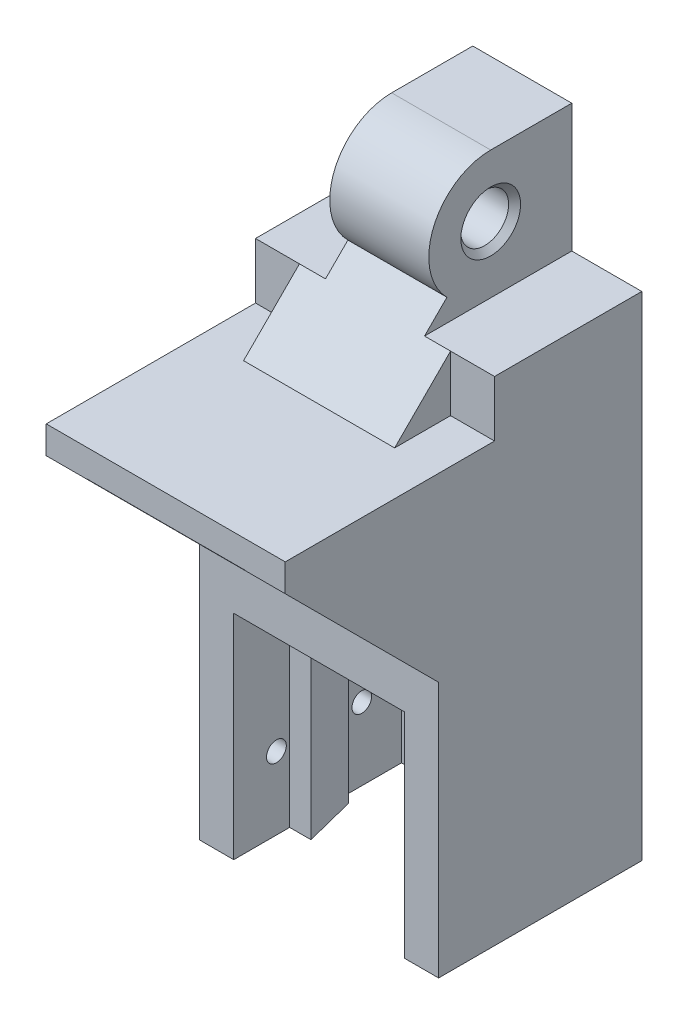
SolidWorks part; units mm, degrees
material "Plastique personnalisé"
ref_plane "前视基准面" through (0, 0, 0) normal (0, 0, 1) x (1, 0, 0)
ref_plane "上视基准面" through (0, 0, 0) normal (0, 1, 0) x (1, 0, 0)
ref_plane "右视基准面" through (0, 0, 0) normal (1, 0, 0) x (0, 0, -1)
sketch "Sketch1" plane through (0, 0, 0) normal (0, 1, 0) x (1, 0, 0)
  line L1 (-13, 14) -> (13, 14)
  line L2 (-13, 14) -> (-13, -14)
  line L3 (-13, -14) -> (13, -14)
  line L4 (13, 14) -> (13, -14)
  line L5 (-13, 14) -> (13, -14) construction
  line L6 (-13, -14) -> (13, 14) construction
  point P0 (0, 0)
  dimension "D1" = 26
  dimension "D2" = 28
extrude "Boss-Extrude1" add sketch "Sketch1" along normal blind 50
sketch "Sketch7" plane through (13, 0, 0) normal (1, 0, 0) x (0, 0, -1)
  line L0 (4.5, 50) -> (-14, 50)
  line L1 (-14, 50) -> (-14, 24)
  line L2 (-14, 50) -> (-14, 0) construction
  line L3 (-14, 24) -> (-0.6265, 37.3735)
  line L4 (7.5, 35.3637) -> (14, 50) construction
  line L6 (14, 50) -> (14, 0) construction
  line L7 (14, 42.5) -> (4.5, 42.5) construction
  line L8 (4.5, 49.75) -> (14, 49.75)
  line L9 (14, 49.75) -> (14, 50)
  line L10 (14, 50) -> (4.5, 50)
  arc A1 (-0.6265, 37.3735) -> (4.5, 49.75) centre (4.5, 42.5) ccw
  dimension "D2" = 7.5
  dimension "D1" = 26
  dimension "D3" = 9.5
  dimension "D4" = 45
extrude "Cut-Extrude3" cut sketch "Sketch7" against normal blind 39
sketch "Sketch14" plane through (0, 0, 0) normal (1, 0, 0) x (0, 0, -1)
  line L0 (14, 49.75) -> (14, 0) construction
  circle A0 centre (4.5, 42.5) radius 7.25
  dimension "D2" = 14.5
  dimension "D1" = 9.5
extrude "Boss-Extrude7" add sketch "Sketch14" against normal blind 5.8 and the other way blind 5.8
mirror "Symétrie1" about plane through (0, 0, 0) normal (1, 0, 0) of "Boss-Extrude7"
sketch "Sketch15" plane through (13, 0, 0) normal (1, 0, 0) x (0, 0, -1)
  line L0 (14, 49.75) -> (14, 0) construction
  line L1 (4.5, 42.5) -> (1.6109, 40.6109) construction
  line L3 (4.5, 49.75) -> (14, 49.75) construction
  circle A1 centre (4.5, 42.5) radius 2.8
  dimension "D1" = 5.6
  dimension "D2" = 9.5
  dimension "D3" = 7.25
extrude "Cut-Extrude4" cut sketch "Sketch15" against normal blind 28
sketch "Sketch16" plane through (13, 0, 0) normal (1, 0, 0) x (0, 0, -1)
  circle A0 centre (4.5, 42.5) radius 5.25
  dimension "D1" = 10.5
sketch "Sketch17" plane through (0, 0, 0) normal (0, -1, 0) x (1, 0, 0)
  line L0 (-9.3, 3.25) -> (-13, 3.25)
  line L2 (9.3, 3.25) -> (9.3, 9.8)
  line L3 (-13, -14) -> (-13, 14) construction
  line L4 (-13, 3.25) -> (-13, 14)
  line L5 (-9.3, 3.25) -> (-9.3, 9.8)
  line L6 (-13, 14) -> (13, 14)
  line L8 (13, 14) -> (13, 3.25)
  line L9 (13, 14) -> (13, -14) construction
  line L10 (13, 3.25) -> (9.3, 3.25)
  line L14 (9.3, 9.8) -> (-9.3, 9.8)
extrude "Cut-Extrude7" cut sketch "Sketch17" against normal through all
sketch "Sketch18" plane through (0, 0, 0) normal (1, 0, 0) x (0, 0, -1)
  line L3 (-2.2308, 35.7692) -> (-5.9308, 32.0692)
  line L6 (-2.2308, 35.7692) -> (-5.9308, 35.7692)
  line L7 (-5.9308, 35.7692) -> (-5.9308, 32.0692)
  dimension "D1" = 3.7
  dimension "D3" = 3.7
sketch "Sketch19" plane through (0, 0, -14) normal (0, 0, -1) x (-1, 0, 0)
  line L0 (-13, 0) -> (13, 0) construction
  circle A0 centre (0, 16) radius 2.15
  point P2 (0, 0)
  dimension "D1" = 4.3
  dimension "D2" = 16
extrude "Cut-Extrude9" cut sketch "Sketch19" against normal blind 50
sketch "Sketch20" plane through (0, 0, -14) normal (0, 0, -1) x (-1, 0, 0)
  circle A0 centre (0, 16) radius 4
  dimension "D1" = 8
extrude "Cut-Extrude10" [suppressed] cut sketch "Sketch20" against normal blind 3
sketch "Esquisse1" plane through (0, 49.75, 0) normal (0, 1, 0) x (1, 0, 0)
  line L2 (-5.8, 4.5) -> (-23.1712, 4.5)
  line L3 (-5.8, 4.5) -> (-5.8, 15.3551)
  line L4 (-5.8, 15.3551) -> (-23.1712, 15.3551)
  line L5 (-23.1712, 4.5) -> (-23.1712, 15.3551)
extrude "Enlèv. mat.-Extru.1" cut sketch "Esquisse1" against normal blind 7.5
mirror "Symétrie3" about plane through (0, 0, 0) normal (1, 0, 0) of "Enlèv. mat.-Extru.1"
extrude "Boss.-Extru.1" [suppressed] add sketch "Sketch18" along normal blind 3.4 and the other way blind 3.4
sketch "Esquisse3" plane through (13, 0, 0) normal (1, 0, 0) x (0, 0, -1)
  line L0 (-3.25, 34.75) -> (14, 34.75)
  line L1 (14, 42.25) -> (14, 0) construction
  line L2 (14, 34.75) -> (14, 43.174)
  line L3 (14, 42.25) -> (14, 49.75) construction
  line L4 (14, 43.174) -> (-3.25, 43.174)
  line L5 (-3.25, 43.174) -> (-3.25, 34.75)
extrude "Enlèv. mat.-Extru.3" cut sketch "Esquisse3" against normal up to vertex (7.2 mm away) up to point (5.8, 37.3735, 0.6265)
mirror "Symétrie4" about plane through (0, 0, 0) normal (1, 0, 0) of "Enlèv. mat.-Extru.3"
sketch "Esquisse43" plane through (0, 0, 9.8) normal (0, 0, 1) x (1, 0, 0)
  line L1 (-9.3, 28.2) -> (-9.3, 0) construction
  line L2 (9.3, 28.2) -> (9.3, 0) construction
  line L3 (-9.3, 25) -> (9.3, 25)
  line L4 (-9.3, 25) -> (-9.3, 7)
  line L5 (-9.3, 7) -> (9.3, 7)
  line L6 (9.3, 25) -> (9.3, 7)
  dimension "D2" = 18
extrude "Enlèv. mat.-Extru.4" cut sketch "Esquisse43" against normal blind 20
sketch "Esquisse45" plane through (0, 0, 0) normal (0, -1, 0) x (1, 0, 0)
  line L0 (-9.3, 3.25) -> (-9.3, 9.8)
  line L1 (-9.3, 9.8) -> (9.3, 9.8)
  line L2 (9.3, 9.8) -> (9.3, 3.25)
  line L3 (9.3, 3.25) -> (13, 3.25)
  line L4 (13, 3.25) -> (13, -14)
  line L5 (13, -14) -> (-13, -14)
  line L6 (-13, -14) -> (-13, 3.25)
  line L7 (-13, 3.25) -> (-9.3, 3.25)
extrude "Boss.-Extru.28" add sketch "Esquisse45" along normal blind 23
sketch "Sketch3" plane through (0, -23, 0) normal (0, 1, 0) x (1, 0, 0)
  line L0 (10, 2.65) -> (10, 9.85)
  line L1 (2.9, 9.85) -> (10, 9.85)
  line L2 (-10, 9.85) -> (-10, 2.65)
  line L3 (-10, 9.85) -> (-2.9, 9.85)
  line L4 (-10, -14.9617) -> (-10, -3.25)
  line L5 (7.5, -3.25) -> (9, 2.65)
  line L6 (-10, -14.9617) -> (10, -14.9617)
  line L7 (2.9, 9.85) -> (2.9, 5.85) construction
  line L8 (-10, -3.25) -> (-7.5028, -3.25) construction
  line L10 (2.9, 5.85) -> (-2.9, 5.85) construction
  line L11 (10, -14.9617) -> (10, -3.25)
  line L12 (10, -3.25) -> (7.5, -3.25)
  line L13 (-10, 2.65) -> (-9, 2.65)
  line L14 (10, 2.65) -> (9, 2.65)
  line L15 (-10, -3.25) -> (-7.5028, -3.25)
  line L16 (-2.9, 9.85) -> (-2.9, 5.85) construction
  line L17 (-7.5028, -3.25) -> (-9, 2.65)
  line L31 (2.9, 9.85) -> (2.9, 5.85)
  line L32 (2.9, 5.85) -> (-2.9, 5.85)
  line L33 (-2.9, 5.85) -> (-2.9, 9.85)
  dimension "D3" = 5.8
  dimension "D4" = 1
  dimension "D5" = 5.9
  dimension "D6" = 7.2
  dimension "D7" = 1
  dimension "D1" = 7.1
  dimension "D2" = 7.1
  dimension "D9" = 7.2
extrude "Enlèv. mat.-Extru.5" cut sketch "Sketch3" along normal blind 25
sketch "Esquisse47" plane through (0, 2, 0) normal (0, -1, 0) x (-1, 0, 0)
  line L0 (0, 0) -> (0, -7.2291) construction
  line L1 (-9, 2.65) -> (-9, 5.85)
  line L2 (-9, 2.65) -> (-7.0167, -5.49)
  line L3 (6.5509, 5.85) -> (9, 5.85)
  line L4 (6.5509, -5.49) -> (7.0167, -5.49)
  line L5 (-6.5509, -5.49) -> (-7.0167, -5.49)
  line L7 (9, 2.65) -> (7.0167, -5.49)
  line L8 (-6.5509, 5.85) -> (-9, 5.85)
  line L9 (9, 2.65) -> (9, 5.85)
  line L10 (2.9, 0.55) -> (2.9, 6.65) construction
  arc A0 (6.5509, -5.49) -> (6.5509, 5.85) centre (9.1283, 0.18) cw
  arc A1 (-6.5509, -5.49) -> (-6.5509, 5.85) centre (-9.1283, 0.18) ccw
extrude "Enlèv. mat.-Extru.6" cut sketch "Esquisse47" against normal blind 7
sketch "Esquisse48" plane through (0, 0, -10.2) normal (0, 0, 1) x (1, 0, 0)
  circle A0 centre (0, 16) radius 4
  dimension "D1" = 8
extrude "Boss.-Extru.29" add sketch "Esquisse48" along normal blind 6
sketch "Esquisse49" [suppressed] plane through (0, 0, -10.2) normal (0, 0, -1) x (-1, 0, 0)
  line L0 (0, 18.15) -> (0, 13.85) construction
  circle A0 centre (0, 16) radius 2.15 construction
  circle A1 centre (0, 16) radius 2.15 construction
  circle A2 centre (0, 16) radius 2.15
extrude "Enlèv. mat.-Extru.7" [suppressed] cut sketch "Esquisse49" against normal blind 5
sketch "Esquisse50" [suppressed] plane through (0, 0, -5.2) normal (0, 0, -1) x (-1, 0, 0)
  circle A0 centre (0, 16) radius 2.15
extrude "Enlèv. mat.-Extru.8" [suppressed] cut sketch "Esquisse50" against normal blind 5
sketch "Esquisse51" plane through (0, 0, -5.85) normal (0, 0, 1) x (1, 0, 0)
  line L0 (2.9, 2) -> (-2.9, 2) construction
  circle A0 centre (0, -8) radius 2.15
  dimension "D1" = 4.3
  dimension "D2" = 10
extrude "Enlèv. mat.-Extru.9" cut sketch "Esquisse51" against normal blind 12 contours A0
sketch "Esquisse52" plane through (0, 0, -14) normal (0, 0, -1) x (-1, 0, 0)
  circle A0 centre (0, -8) radius 3.5
  dimension "D1" = 7
extrude "Enlèv. mat.-Extru.10" [suppressed] cut sketch "Esquisse52" against normal blind 3 contours A0
sketch "Esquisse53" plane through (-9.3, 0, 0) normal (-1, 0, 0) x (0, 0, 1)
  line L1 (9.8, 28.2) -> (3.25, 28.2)
  line L2 (9.8, 28.2) -> (9.8, 2)
  line L3 (9.8, 2) -> (3.25, 2)
  line L4 (3.25, 28.2) -> (3.25, 2)
extrude "Boss.-Extru.30" add sketch "Esquisse53" along normal up to vertex (3.7 mm away) up to point (-13, 34.75, 3.25)
sketch "Esquisse54" plane through (9.3, 0, 0) normal (1, 0, 0) x (0, 0, -1)
  line L1 (-9.8, 28.2) -> (-3.25, 28.2)
  line L2 (-9.8, 28.2) -> (-9.8, 2)
  line L3 (-9.8, 2) -> (-3.25, 2)
  line L4 (-3.25, 28.2) -> (-3.25, 2)
extrude "Boss.-Extru.31" add sketch "Esquisse54" along normal up to vertex (3.7 mm away) up to point (13, -23, 3.25)
sketch "Esquisse55" plane through (0, 0, 3.25) normal (0, 0, 1) x (1, 0, 0)
  line L0 (-7.5028, -23) -> (-13, -23) construction
  line L1 (-13, 2) -> (-10, 2)
  line L2 (-13, 2) -> (-13, -23)
  line L3 (-13, -23) -> (-10, -23)
  line L4 (-10, 2) -> (-10, -23)
  line L5 (13, -23) -> (7.5, -23) construction
  line L6 (13, 2) -> (10, 2)
  line L7 (13, 2) -> (13, -23)
  line L8 (13, -23) -> (10, -23)
  line L9 (10, 2) -> (10, -23)
  dimension "D1" = 3
  dimension "D2" = 3
extrude "Boss.-Extru.32" add sketch "Esquisse55" along normal up to vertex (6.55 mm away) up to point (-13, 2, 9.8)
sketch "Esquisse56" plane through (-13, 0, 0) normal (-1, 0, 0) x (0, 0, 1)
  line L0 (9.8, -23) -> (9.8, 28.2) construction
  line L2 (9.8, -23) -> (-14, -23) construction
  circle A0 centre (-5.2, -14.5) radius 1.15
  circle A1 centre (4.8, -14.5) radius 1.16
  dimension "D1" = 2.3
  dimension "D2" = 2.32
  dimension "D3" = 10
  dimension "D4" = 5
  dimension "D5" = 8.5
extrude "Enlèv. mat.-Extru.11" cut sketch "Esquisse56" against normal blind 10
chamfer "Chanfrein1" distance 0.7 angle 45 2 edges at (5.8, 42.5, -7.3) (-5.8, 42.5, -7.3)
sketch "Esquisse57" plane through (0, 0, -10.2) normal (0, 0, -1) x (-1, 0, 0)
  circle A0 centre (0, 16) radius 2.15
extrude "Enlèv. mat.-Extru.12" cut sketch "Esquisse57" against normal blind 10
sketch "Esquisse58" plane through (-13, 0, 0) normal (-1, 0, 0) x (0, 0, 1)
  line L0 (-14, 34.75) -> (3.25, 34.75)
  line L1 (3.25, 34.75) -> (3.25, 28.2)
  line L2 (3.25, 28.2) -> (9.8, 28.2)
  line L3 (9.8, 28.2) -> (9.8, -23)
  line L4 (9.8, -23) -> (-14, -23)
  line L5 (-14, -23) -> (-14, 34.75)
  circle A0 centre (-5.2, -14.5) radius 1.15
  circle A1 centre (4.8, -14.5) radius 1.16
extrude "Boss.-Extru.33" add sketch "Esquisse58" along normal blind 1
sketch "Esquisse59" plane through (13, 0, 0) normal (1, 0, 0) x (0, 0, -1)
  line L0 (-3.25, 28.2) -> (-3.25, 34.75)
  line L1 (-3.25, 34.75) -> (14, 34.75)
  line L2 (14, 34.75) -> (14, -23)
  line L3 (14, -23) -> (-9.8, -23)
  line L4 (-9.8, -23) -> (-9.8, 28.2)
  line L5 (-9.8, 28.2) -> (-3.25, 28.2)
extrude "Boss.-Extru.34" add sketch "Esquisse59" along normal blind 1
sketch "Esquisse60" plane through (0, 0, 9.8) normal (0, 0, 1) x (1, 0, 0)
  line L0 (-9.3, 28.2) -> (9.3, 28.2)
sketch "Esquisse61" plane through (0, 0, 3.25) normal (0, 0, 1) x (1, 0, 0)
  line L0 (-9.3, 34.75) -> (-8.85, 34.75)
  line L1 (-5.8, 34.75) -> (-9.3, 34.75) construction
  line L2 (-9.3, 34.75) -> (-9.3, 28.2)
  line L3 (-9.3, 28.2) -> (-8.85, 28.2)
  line L4 (9.3, 34.75) -> (9.3, 28.2)
  line L5 (-8.85, 34.75) -> (-8.85, 28.2)
  line L6 (8.85, 34.75) -> (9.3, 34.75)
  line L7 (8.85, 34.75) -> (8.85, 28.2)
  line L8 (8.85, 28.2) -> (9.3, 28.2)
  dimension "D1" = 0.45
  dimension "D2" = 0.45
extrude "Enlèv. mat.-Extru.13" cut sketch "Esquisse61" along normal blind 15
sketch "Esquisse62" plane through (0, 0, 9.8) normal (0, 0, 1) x (1, 0, 0)
  line L0 (-9.3, 7) -> (-14, 7)
  line L1 (-14, -23) -> (-14, 28.2) construction
  line L2 (-14, 7) -> (-14, 28.2)
  line L3 (-14, 28.2) -> (14, 28.2)
  line L4 (14, 28.2) -> (14, 7)
  line L5 (14, 28.2) -> (14, -23) construction
  line L6 (14, 7) -> (9.3, 7)
  line L7 (9.3, 7) -> (9.3, 25)
  line L8 (9.3, 25) -> (-9.3, 25)
  line L9 (-9.3, 25) -> (-9.3, 7)
extrude "Boss.-Extru.35" add sketch "Esquisse62" along normal blind 25
sketch "Esquisse63" plane through (14, 0, 0) normal (1, 0, 0) x (0, 0, -1)
  line L0 (-9.8, 7) -> (-34.6367, 31.8367)
  line L2 (-34.8, 7) -> (-9.8, 7) construction
  line L3 (-34.6367, 31.8367) -> (-43.13, 15.7591)
  line L4 (-43.13, 15.7591) -> (-32.7852, -2.7315)
  line L5 (-32.7852, -2.7315) -> (-31.8038, -2.7315)
  line L6 (-9.8, 7) -> (-31.8038, -2.7315)
  dimension "D1" = 45
extrude "Enlèv. mat.-Extru.14" cut sketch "Esquisse63" against normal blind 41
sketch "Esquisse64" plane through (-14, 0, 0) normal (-1, 0, 0) x (0, 0, 1)
  line L0 (27.7664, 33.2832) -> (27.7664, 19.4569)
  line L1 (27.7664, 33.2832) -> (40.1126, 32.6315)
  line L2 (40.1126, 32.6315) -> (34.6576, 15.9676)
  line L3 (34.6576, 15.9676) -> (27.7664, 19.4569)
  line L4 (27.7664, 19.4569) -> (27.7828, 19.1061)
  line M3 (9.8, 7) -> (31, 28.2)
  line M4 (31, 28.2) -> (3.25, 28.2)
extrude "Enlèv. mat.-Extru.15" cut sketch "Esquisse64" against normal blind 33 contours L0 M4 M3 region at (-14, 27.1221, 28.8443)
